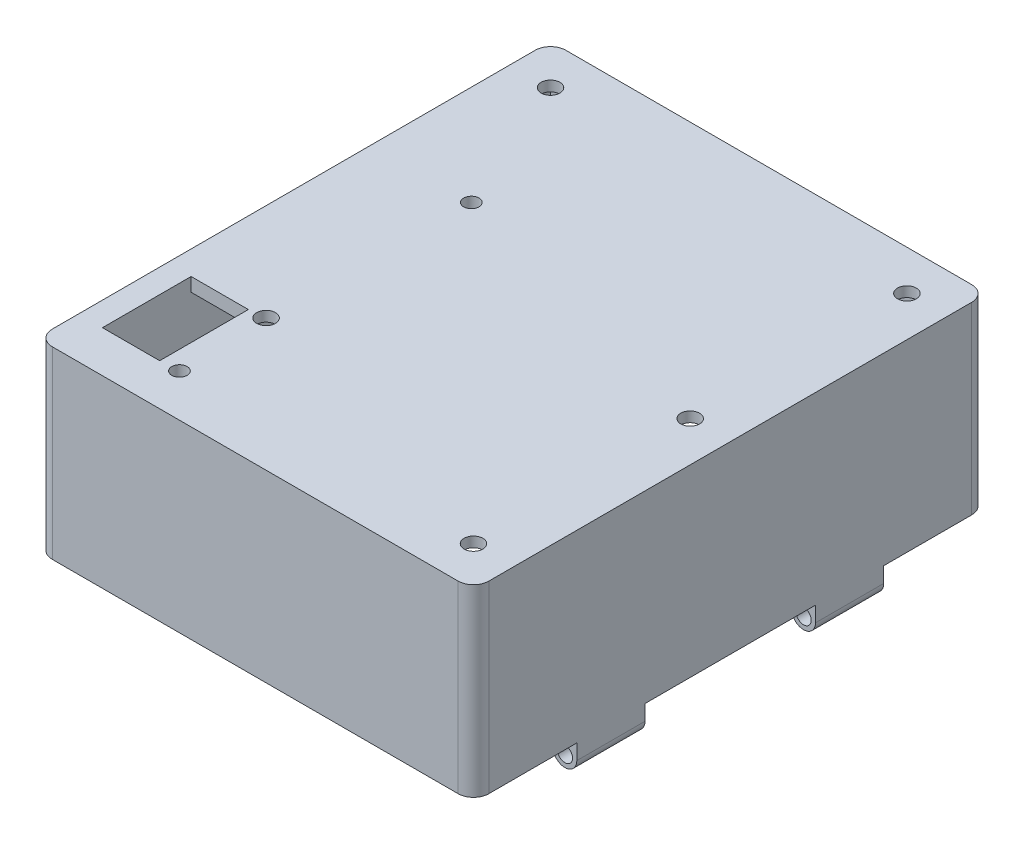
SolidWorks part; units mm, degrees
ref_plane "Front Plane" through (0, 0, 0) normal (0, 0, 1) x (1, 0, 0)
ref_plane "Top Plane" through (0, 0, 0) normal (0, 1, 0) x (1, 0, 0)
ref_plane "Right Plane" through (0, 0, 0) normal (1, 0, 0) x (0, 0, -1)
sketch "Sketch1" plane through (0, 16.9149, 0) normal (0, -1, 0) x (1, 0, 0)
  line L0 (56.8579, 38.1999) -> (56.8579, -32.5943) construction
  line L1 (-4.8921, 40.4499) -> (54.6079, 40.4499) construction
  line L3 (-4.8921, -34.8443) -> (54.6079, -34.8443) construction
  line L4 (56.8579, 38.1999) -> (56.8579, -32.5943)
  line L5 (-4.8921, 40.4499) -> (54.6079, 40.4499)
  line L7 (-4.8921, -34.8443) -> (54.6079, -34.8443)
  line L8 (-7.1421, 38.1999) -> (-7.1421, -32.5943)
  arc A0 (54.6079, -34.8443) -> (56.8579, -32.5943) centre (54.6079, -32.5943) ccw construction
  arc A1 (56.8579, 38.1999) -> (54.6079, 40.4499) centre (54.6079, 38.1999) ccw construction
  arc A3 (-7.1421, -32.5943) -> (-4.8921, -34.8443) centre (-4.8921, -32.5943) ccw construction
  arc A4 (54.6079, -34.8443) -> (56.8579, -32.5943) centre (54.6079, -32.5943) ccw
  arc A5 (56.8579, 38.1999) -> (54.6079, 40.4499) centre (54.6079, 38.1999) ccw
  arc A7 (-7.1421, -32.5943) -> (-4.8921, -34.8443) centre (-4.8921, -32.5943) ccw
  arc A8 (-4.8921, 40.4499) -> (-7.1421, 38.1999) centre (-4.8921, 38.1999) ccw construction
  arc A9 (-4.8921, 40.4499) -> (-7.1421, 38.1999) centre (-4.8921, 38.1999) ccw
extrude "Extrude Base" add sketch "Sketch1" along normal blind 2
sketch "Sketch2" plane through (0, 14.9149, 0) normal (0, -1, 0) x (1, 0, 0)
  line L0 (53.3579, 36.9499) -> (-3.6421, 36.9499)
  line L1 (-3.6421, 36.9499) -> (-3.6421, -31.3443)
  line L2 (-3.6421, -31.3443) -> (53.3579, -31.3443)
  line L3 (53.3579, -31.3443) -> (53.3579, 36.9499)
  line L4 (56.8579, -32.5943) -> (56.8579, 38.1999)
  line L5 (54.6079, 40.4499) -> (-4.8921, 40.4499)
  line L6 (-7.1421, 38.1999) -> (-7.1421, -32.5943)
  line L7 (-4.8921, -34.8443) -> (54.6079, -34.8443)
  line L8 (56.8579, -32.5943) -> (56.8579, 38.1999)
  line L9 (54.6079, 40.4499) -> (-4.8921, 40.4499)
  line L10 (-7.1421, 38.1999) -> (-7.1421, -32.5943)
  line L11 (-4.8921, -34.8443) -> (54.6079, -34.8443)
  arc A0 (-3.6421, 36.9499) -> (-3.6421, 36.9499) centre (-3.6421, 36.9499) ccw
  arc A1 (-3.6421, -31.3443) -> (-3.6421, -31.3443) centre (-3.6421, -31.3443) ccw
  arc A2 (53.3579, -31.3443) -> (53.3579, -31.3443) centre (53.3579, -31.3443) ccw
  arc A3 (53.3579, 36.9499) -> (53.3579, 36.9499) centre (53.3579, 36.9499) ccw
  arc A4 (54.6079, -34.8443) -> (56.8579, -32.5943) centre (54.6079, -32.5943) ccw
  arc A5 (56.8579, 38.1999) -> (54.6079, 40.4499) centre (54.6079, 38.1999) ccw
  arc A6 (-4.8921, 40.4499) -> (-7.1421, 38.1999) centre (-4.8921, 38.1999) ccw
  arc A7 (-7.1421, -32.5943) -> (-4.8921, -34.8443) centre (-4.8921, -32.5943) ccw
  arc A8 (54.6079, -34.8443) -> (56.8579, -32.5943) centre (54.6079, -32.5943) ccw
  arc A9 (56.8579, 38.1999) -> (54.6079, 40.4499) centre (54.6079, 38.1999) ccw
  arc A11 (-7.1421, -32.5943) -> (-4.8921, -34.8443) centre (-4.8921, -32.5943) ccw
  arc A16 (-4.8921, 40.4499) -> (-7.1421, 38.1999) centre (-4.8921, 38.1999) ccw construction
  arc A17 (-4.8921, 40.4499) -> (-7.1421, 38.1999) centre (-4.8921, 38.1999) ccw
  dimension "D2" = 3.5
extrude "Extrude Walls" add sketch "Sketch2" along normal blind 25
sketch "Sketch3" plane through (0, 14.9149, 0) normal (0, -1, 0) x (1, 0, 0)
  line L1 (-3.6421, 34.3499) -> (4.7489, 34.3499)
  line L2 (-3.6421, 34.3499) -> (-3.6421, 21.3499)
  line L3 (-3.6421, 21.3499) -> (4.7489, 21.3499)
  line L4 (53.3579, -31.3443) -> (53.3579, 36.9499)
  line L5 (53.3579, 36.9499) -> (-3.6421, 36.9499)
  line L6 (-3.6421, 36.9499) -> (-3.6421, -31.3443)
  line L7 (-3.6421, -31.3443) -> (53.3579, -31.3443)
  line L8 (53.3579, -31.3443) -> (53.3579, 36.9499) construction
  line L9 (53.3579, 36.9499) -> (-3.6421, 36.9499) construction
  line L10 (-3.6421, 36.9499) -> (-3.6421, -31.3443) construction
  line L11 (-3.6421, -31.3443) -> (53.3579, -31.3443) construction
  line L12 (4.7489, 34.3499) -> (4.7489, 21.3499)
  line L16 (12.7778, 29.78) -> (12.7778, 34.7643)
  line L17 (4.7489, 29.78) -> (12.7778, 29.78)
  line L18 (4.7489, 21.3499) -> (4.7489, 29.78)
  line L19 (-3.6421, 21.3499) -> (4.7489, 21.3499)
  line L20 (-3.6421, 34.3499) -> (-3.6421, 21.3499)
  line L21 (4.7489, 34.3499) -> (-3.6421, 34.3499)
  line L22 (4.7489, 34.7643) -> (4.7489, 34.3499)
  line L23 (12.7778, 34.7643) -> (4.7489, 34.7643)
  line L24 (12.7778, 29.78) -> (12.7778, 34.7643) construction
  line L25 (4.7489, 29.78) -> (12.7778, 29.78) construction
  line L26 (4.7489, 21.3499) -> (4.7489, 29.78) construction
  line L27 (-3.6421, 21.3499) -> (4.7489, 21.3499) construction
  line L28 (-3.6421, 34.3499) -> (-3.6421, 21.3499) construction
  line L29 (4.7489, 34.3499) -> (-3.6421, 34.3499) construction
  line L30 (4.7489, 34.7643) -> (4.7489, 34.3499) construction
  line L31 (12.7778, 34.7643) -> (4.7489, 34.7643) construction
  dimension "D1" = 0
  dimension "D2" = 0
extrude "Cut USB Hole" cut sketch "Sketch3" against normal through all
sketch "Sketch4" plane through (0, 14.9149, 0) normal (0, -1, 0) x (1, 0, 0)
  line L4 (39.7079, 22.2499) -> (39.7079, 26.2499)
  line L5 (28.7079, 22.2499) -> (39.7079, 22.2499)
  line L6 (28.7079, 26.2499) -> (28.7079, 22.2499)
  line L7 (39.7079, 26.2499) -> (28.7079, 26.2499)
  line L8 (39.7079, 22.2499) -> (39.7079, 26.2499) construction
  line L9 (28.7079, 22.2499) -> (39.7079, 22.2499) construction
  line L10 (28.7079, 26.2499) -> (28.7079, 22.2499) construction
  line L11 (39.7079, 26.2499) -> (28.7079, 26.2499) construction
  line L12 (39.7079, 29.4499) -> (39.7079, 33.4499)
  line L13 (28.7079, 29.4499) -> (39.7079, 29.4499)
  line L14 (28.7079, 33.4499) -> (28.7079, 29.4499)
  line L15 (39.7079, 33.4499) -> (28.7079, 33.4499)
  line L16 (12.7778, 29.78) -> (12.7778, 34.7643)
  line L17 (4.7489, 29.78) -> (12.7778, 29.78)
  line L18 (4.7489, 21.3499) -> (4.7489, 29.78)
  line L19 (-3.6421, 21.3499) -> (4.7489, 21.3499)
  line L20 (-3.6421, 34.3499) -> (-3.6421, 21.3499)
  line L21 (4.7489, 34.3499) -> (-3.6421, 34.3499)
  line L22 (4.7489, 34.7643) -> (4.7489, 34.3499)
  line L23 (12.7778, 34.7643) -> (4.7489, 34.7643)
  line L24 (12.7778, 29.78) -> (12.7778, 34.7643) construction
  line L25 (4.7489, 29.78) -> (12.7778, 29.78) construction
  line L26 (4.7489, 21.3499) -> (4.7489, 29.78) construction
  line L27 (-3.6421, 21.3499) -> (4.7489, 21.3499) construction
  line L28 (-3.6421, 34.3499) -> (-3.6421, 21.3499) construction
  line L29 (4.7489, 34.3499) -> (-3.6421, 34.3499) construction
  line L30 (4.7489, 34.7643) -> (4.7489, 34.3499) construction
  line L31 (12.7778, 34.7643) -> (4.7489, 34.7643) construction
  line L32 (39.7079, 29.4499) -> (39.7079, 33.4499) construction
  line L33 (28.7079, 29.4499) -> (39.7079, 29.4499) construction
  line L34 (28.7079, 33.4499) -> (28.7079, 29.4499) construction
  line L35 (39.7079, 33.4499) -> (28.7079, 33.4499) construction
  line L36 (28.7786, -1.4633) -> (28.7786, 5.1247)
  line L37 (20.4164, -1.4633) -> (28.7786, -1.4633)
  line L38 (20.4164, 5.1247) -> (20.4164, -1.4633)
  line L39 (28.7786, 5.1247) -> (20.4164, 5.1247)
  line L40 (28.7786, -1.4633) -> (28.7786, 5.1247) construction
  line L41 (20.4164, -1.4633) -> (28.7786, -1.4633) construction
  line L42 (20.4164, 5.1247) -> (20.4164, -1.4633) construction
  line L43 (28.7786, 5.1247) -> (20.4164, 5.1247) construction
  line L44 (28.7786, 9.2809) -> (28.7786, 15.8689)
  line L45 (20.4164, 9.2809) -> (28.7786, 9.2809)
  line L46 (20.4164, 15.8689) -> (20.4164, 9.2809)
  line L47 (28.7786, 15.8689) -> (20.4164, 15.8689)
  line L48 (28.7786, 9.2809) -> (28.7786, 15.8689) construction
  line L49 (20.4164, 9.2809) -> (28.7786, 9.2809) construction
  line L50 (20.4164, 15.8689) -> (20.4164, 9.2809) construction
  line L51 (28.7786, 15.8689) -> (20.4164, 15.8689) construction
  line L56 (-3.6421, 34.3499) -> (4.7489, 34.3499)
  line L57 (4.7489, 34.3499) -> (4.7489, 21.3499)
  line L58 (4.7489, 21.3499) -> (-3.6421, 21.3499)
  line L59 (-3.6421, 21.3499) -> (-3.6421, -31.3443)
  line L60 (-3.6421, -31.3443) -> (53.3579, -31.3443)
  line L61 (53.3579, -31.3443) -> (53.3579, 36.9499)
  line L62 (53.3579, 36.9499) -> (-3.6421, 36.9499)
  line L63 (-3.6421, 36.9499) -> (-3.6421, 34.3499)
  line L64 (-3.6421, 34.3499) -> (4.7489, 34.3499)
  line L65 (4.7489, 34.3499) -> (4.7489, 21.3499)
  line L66 (4.7489, 21.3499) -> (-3.6421, 21.3499)
  line L67 (-3.6421, 21.3499) -> (-3.6421, -31.3443) construction
  line L68 (-3.6421, -31.3443) -> (53.3579, -31.3443) construction
  line L69 (53.3579, -31.3443) -> (53.3579, 36.9499) construction
  line L70 (53.3579, 36.9499) -> (-3.6421, 36.9499) construction
  line L71 (-3.6421, 36.9499) -> (-3.6421, 34.3499) construction
  line L740 (-3.6421, 18.7499) -> (34.5079, 18.7499) construction
  line L741 (-3.6421, 18.7499) -> (34.5079, 18.7499) construction
  circle A0 centre (50.9829, 34.5749) radius 1.375
  circle A1 centre (50.9829, -28.9693) radius 1.375
  circle A2 centre (-1.2671, -28.9693) radius 1.375
  circle A5 centre (50.9829, 2.8028) radius 1.375
  circle A6 centre (7.1239, 21.1249) radius 1.375
  point P49 (53.3579, 2.8028)
  dimension "D7" = 2.75
  dimension "D8" = 2.75
  dimension "D9" = 2.75
  dimension "D10" = 2.75
  dimension "D11" = 2.75
  dimension "D13" = 2.375
  dimension "D14" = 2.375
  dimension "D17" = 2.375
  dimension "D15" = 2.375
  dimension "D12" = 2.375
  dimension "D16" = 2.375
  dimension "D6" = 0
extrude "Cut Connecting Thru Holes" cut sketch "Sketch4" against normal through all contours A0 | A5 | A2 | A1 | A6 region at (50.9829, 14.9149, 34.5749) region at (50.9829, 14.9149, -28.9693) region at (-1.2671, 14.9149, -28.9693) region at (50.9829, 14.9149, 2.8028) region at (7.1239, 14.9149, 21.1249)
sketch "Sketch5" plane through (0, 14.9149, 0) normal (0, -1, 0) x (1, 0, 0)
  circle A0 centre (50.9829, -28.9693) radius 1.375 construction
  circle A1 centre (50.9829, 2.8028) radius 1.375 construction
  circle A2 centre (50.9829, 34.5749) radius 1.375 construction
  circle A3 centre (-1.2671, -28.9693) radius 1.375 construction
  circle A6 centre (50.9829, -28.9693) radius 1.375 construction
  circle A7 centre (50.9829, 2.8028) radius 1.375 construction
  circle A8 centre (50.9829, 34.5749) radius 1.375 construction
  circle A9 centre (-1.2671, -28.9693) radius 1.375 construction
  circle A13 centre (50.9829, 34.5749) radius 2.25
  circle A14 centre (50.9829, 2.8028) radius 2.25
  circle A16 centre (-1.2671, -28.9693) radius 2.25
  circle A17 centre (50.9829, -28.9693) radius 2.25
  circle A18 centre (7.1239, 21.1249) radius 1.375 construction
  circle A19 centre (7.1239, 21.1249) radius 1.375 construction
  circle A20 centre (7.1239, 21.1249) radius 2.25
  circle M33 centre (7.1239, 21.1249) radius 1.375
  dimension "D2" = 4.5
  dimension "D3" = 4.5
  dimension "D4" = 4.5
  dimension "D5" = 4.5
  dimension "D1" = 4.5
extrude "Cut-Extrude3" cut sketch "Sketch5" against normal blind 0.5 contours A20 M33 | A13 | A14 | A17 | A16 region at (4.9375, 14.9149, 21.1249)
sketch "Sketch6" plane through (0, 14.9149, 0) normal (0, -1, 0) x (1, 0, 0)
  circle A0 centre (7.4989, 34.1999) radius 1.375 construction
  circle A1 centre (7.4989, -8.5943) radius 1.375 construction
  circle A2 centre (7.4989, 34.1999) radius 1.375 construction
  circle A3 centre (7.4989, -8.5943) radius 1.375 construction
  circle A4 centre (7.4989, 34.1999) radius 1.125
  circle A5 centre (7.4989, -8.5943) radius 1.125
  dimension "D1" = 2.25
  dimension "D2" = 2.25
extrude "Cut Cable Cover Bottom" cut sketch "Sketch6" against normal through all
sketch "Sketch7" plane through (-3.6421, 0, 0) normal (1, 0, 0) x (0, 0, -1)
  circle A0 centre (8.5943, 7.1649) radius 1.375 construction
  circle A1 centre (-34.1999, 7.1649) radius 1.375 construction
  circle A2 centre (8.5943, 7.1649) radius 1.375 construction
  circle A3 centre (-34.1999, 7.1649) radius 1.375 construction
  circle A4 centre (8.5943, 7.1649) radius 1.125
  circle A5 centre (-34.1999, 7.1649) radius 1.125
  dimension "D1" = 2.25
  dimension "D2" = 2.25
extrude "Cut Cable Cover Side" cut sketch "Sketch7" against normal blind 2
sketch "Sketch8" plane through (0, -10.0851, 0) normal (0, -1, 0) x (1, 0, 0)
  line L0 (53.3579, -31.3443) -> (53.3579, 36.9499) construction
  line L1 (53.3579, -9.6972) -> (56.8579, -9.6972)
  line L2 (53.3579, -9.6972) -> (53.3579, -19.6972)
  line L3 (53.3579, -19.6972) -> (56.8579, -19.6972)
  line L4 (56.8579, -9.6972) -> (56.8579, -19.6972)
  line L5 (56.8579, -32.5943) -> (56.8579, 38.1999) construction
  line L6 (56.8579, 2.8028) -> (53.3579, 2.8028) construction
  line L7 (56.8579, 15.3028) -> (56.8579, 25.3028)
  line L8 (53.3579, 25.3028) -> (56.8579, 25.3028)
  line L9 (53.3579, 15.3028) -> (53.3579, 25.3028)
  line L10 (53.3579, 15.3028) -> (56.8579, 15.3028)
  dimension "D1" = 10
  dimension "D2" = 12.5
extrude "Extrude Hinge" add sketch "Sketch8" along normal blind 4
sketch "Sketch9" plane through (0, 0, -19.6972) normal (0, 0, -1) x (-1, 0, 0)
  line L3 (-53.3579, -14.0851) -> (-56.8579, -14.0851) construction
  circle A0 centre (-55.1079, -12.3351) radius 1.125
  point P5 (-55.1079, -14.0851)
  dimension "D1" = 2.25
  dimension "D2" = 1.75
extrude "Cut Hinge Hole" cut sketch "Sketch9" against normal through all
fillet "Fillet Hinge" radius 1.75 4 edges at (56.8579, -14.0851, 20.3028) (53.3579, -14.0851, 20.3028) (56.8579, -14.0851, -14.6972) (53.3579, -14.0851, -14.6972)
sketch "Sketch10" plane through (-3.6421, 0, 0) normal (1, 0, 0) x (0, 0, -1)
  line L0 (-36.9499, -10.0851) -> (31.3443, -10.0851) construction
  line L1 (-22.8028, -0.0851) -> (17.1972, -0.0851)
  line L2 (-22.8028, -0.0851) -> (-22.8028, -5.0851)
  line L3 (-22.8028, -5.0851) -> (17.1972, -5.0851)
  line L4 (17.1972, -0.0851) -> (17.1972, -5.0851)
  point P4 (-2.8028, -10.0851)
  point P5 (-2.8028, -5.0851)
  dimension "D1" = 40
  dimension "D2" = 5
  dimension "D3" = 5
extrude "Cut Notch" cut sketch "Sketch10" against normal blind 1.5 contours L3 L4 L1 L2
sketch "Sketch11" plane through (0, 0, -31.3443) normal (0, 0, 1) x (1, 0, 0)
  line L0 (-3.6421, -10.0851) -> (53.3579, -10.0851) construction
  line L1 (16.3579, -5.0851) -> (6.3579, -5.0851)
  line L2 (16.3579, -5.0851) -> (16.3579, -0.0851)
  line L3 (16.3579, -0.0851) -> (6.3579, -0.0851)
  line L4 (6.3579, -5.0851) -> (6.3579, -0.0851)
  line L5 (-3.6421, -10.0851) -> (-3.6421, 14.9149) construction
  dimension "D3" = 5
  dimension "D1" = 5
  dimension "D2" = 10
  dimension "D4" = 10
extrude "Cut Side Notch" cut sketch "Sketch11" against normal blind 1.5
ref_plane "Plane1" through (0, 0, 2.8028) normal (0, 0, -1) x (-1, 0, 0)
mirror "Mirror Side Notch" about plane through (0, 0, 2.8028) normal (0, 0, -1) of "Cut Side Notch"
fillet "Fillet Notch" radius 1.5 6 edges at (-5.1421, -5.0851, 2.8028) (-5.1421, -0.0851, 2.8028) (11.3579, -5.0851, -32.8443) (11.3579, -0.0851, -32.8443) (11.3579, -5.0851, 38.4499) (11.3579, -0.0851, 38.4499)
equation "\"case height\" = 25"
equation "\"base thickness\"= 2"
equation "\"case thickness\"= 3.5"
equation "\"D1@Extrude Base\" = \"base thickness\""
equation "\"D2@Sketch2\"=\"case thickness\""
equation "\"D1@Extrude Walls\" = \"case height\""
equation "\"tap hole size\"=2.25"
equation "\"through hole size\"= 2.75"
equation "\"D8@Sketch4\"=\"through hole size\""
equation "\"D9@Sketch4\"=\"through hole size\""
equation "\"D10@Sketch4\"=\"through hole size\""
equation "\"tolerance\"=0.5"
equation "\"hole to wall distance\"= \"through hole size\" / 2 + 1"
equation "\"D13@Sketch4\"=\"hole to wall distance\""
equation "\"D14@Sketch4\"=\"hole to wall distance\""
equation "\"D17@Sketch4\"=\"hole to wall distance\""
equation "\"D15@Sketch4\"=\"hole to wall distance\""
equation "\"screw head size\"= 4.5"
equation "\"D2@Sketch5\"=\"screw head size\""
equation "\"D3@Sketch5\"=\"screw head size\""
equation "\"D4@Sketch5\"=\"screw head size\""
equation "\"D5@Sketch5\"=\"screw head size\""
equation "\"screw head depth\"= 0.5"
equation "\"D1@Cut-Extrude3\"=\"screw head depth\""
equation "\"D1@Sketch6\"=\"tap hole size\""
equation "\"D2@Sketch6\"=\"tap hole size\""
equation "\"D1@Sketch7\"=\"tap hole size\""
equation "\"D2@Sketch7\"=\"tap hole size\""
equation "\"side cover screw depth\"=2"
equation "\"D1@Cut Cable Cover Side\" = \"side cover screw depth\""
equation "\"D11@Sketch4\"=\"through hole size\""
equation "\"D12@Sketch4\"=\"hole to wall distance\""
equation "\"D16@Sketch4\"=\"hole to wall distance\""
equation "\"D1@Sketch5\"=\"screw head size\""
equation "\"hinge width\"=10"
equation "\"D1@Sketch8\"=\"hinge width\""
equation "\"hinge gap\"=12.5"
equation "\"D2@Sketch8\"=\"hinge gap\""
equation "\"hinge height\" = 4"
equation "\"D1@Extrude Hinge\" = \"hinge height\""
equation "\"D1@Sketch9\"=\"tap hole size\""
equation "\"D1@Fillet Hinge\"=\"case thickness\"/2"
equation "\"notch depth\"=1.5"
equation "\"D1@Cut Notch\" = \"notch depth\""
equation "\"D1@Fillet Notch\"=\"notch depth\""
equation "\"notch height\"=5"
equation "\"D2@Sketch10\"=\"notch height\""
equation "\"notch offset\"=5"
equation "\"D3@Sketch10\"=\"notch offset\""
equation "\"notch width\"=40"
equation "\"D1@Sketch10\"=\"notch width\""
equation "\"D1@Sketch11\"=\"notch height\""
equation "\"D2@Sketch11\"=\"notch width\"/4"
equation "\"D3@Sketch11\"=\"notch offset\""
equation "\"D4@Sketch11\"=\"notch offset\"*2"
equation "\"D1@Cut Side Notch\" = \"notch depth\""
